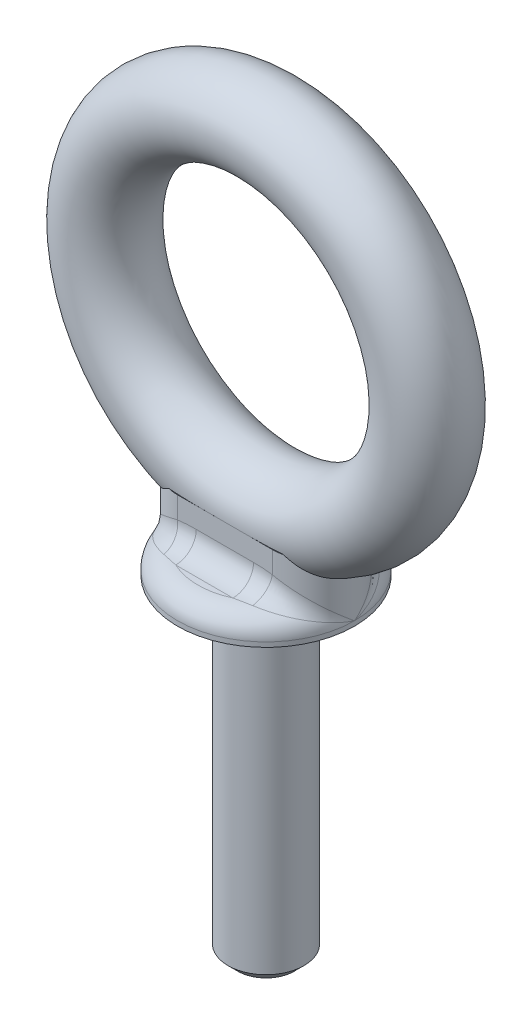
SolidWorks part; units mm, degrees
ref_plane "Front Plane" through (0, 0, 0) normal (0, 0, 1) x (1, 0, 0)
ref_plane "Top Plane" through (0, 0, 0) normal (0, 1, 0) x (1, 0, 0)
ref_plane "Right Plane" through (0, 0, 0) normal (1, 0, 0) x (0, 0, -1)
sketch "Sketch1" plane through (0, 0, 0) normal (0, 0, 1) x (1, 0, 0)
  line L0 (0, -26) -> (0, 0) construction
  line L1 (0, 0) -> (0, 2) construction
  line L2 (0, 2) -> (0, 8.5) construction
  line L3 (0, 8.5) -> (0, 27.5) construction
  line L4 (0, 27.5) -> (0, 34) construction
  line L5 (-3, -26) -> (3, -26) construction
  line L6 (-7, 0) -> (7, 0) construction
  line L7 (-3, 0) -> (3, 0) construction
  circle A0 centre (0, 18) radius 16 construction
  circle A1 centre (0, 18) radius 9.5 construction
  circle A2 centre (0, 30.75) radius 3.25 construction
  circle A3 centre (0, 5.25) radius 3.25 construction
  point P9 (0, 0)
  dimension "Eye Dia." = 19
  dimension "OD" = 32
  dimension "Dia." = 6.5
  dimension "Thread Size" = 6
  dimension "Thread Lg." = 26
  dimension "Shank Lg." = 26
  dimension "Overall Lg." = 60
  dimension "Shoulder Dia." = 14
sketch "Sketch2" plane through (0, 0, 0) normal (1, 0, 0) x (0, 0, -1)
  line L0 (-3.25, 18) -> (3.25, 18) construction
  line L1 (0, 34) -> (0, 27.5) construction
  line L2 (-3.25, 30.75) -> (3.25, 30.75) construction
  circle A0 centre (0, 30.75) radius 3.25
revolve "Revolve1" add sketch "Sketch2" angle 360 about L0
sketch "Sketch3" plane through (0, 0, 0) normal (0, 0, 1) x (1, 0, 0)
  line L0 (-7, 0) -> (0, 0)
  line L1 (0, 0) -> (0, 2)
  line L4 (-7, 0) -> (-7, 2)
  line L5 (0, 2) -> (-7, 2)
revolve "Revolve2" add sketch "Sketch3" angle 360 about L1
fillet "Fillet1" radius 1.625 1 edges at (7, 2, 0)
sketch "Sketch4" plane through (0, 0, 0) normal (0, 1, 0) x (1, 0, 0)
  line L0 (-3.75, 0) -> (3.75, 0) construction
  line L1 (-3.75, 3.25) -> (3.75, 3.25)
  line L2 (-3.75, -3.25) -> (3.75, -3.25)
  arc A0 (-3.75, 3.25) -> (-3.75, -3.25) centre (-3.75, 0) ccw
  arc A1 (3.75, -3.25) -> (3.75, 3.25) centre (3.75, 0) ccw
  circle A2 centre (0, 0) radius 7 construction
  point P2 (0, 0)
extrude "Boss-Extrude3" add sketch "Sketch4" along normal up to vertex (5.25 mm away) up to point (0, 5.25, 0)
fillet "Fillet2" radius 1.625 8 edges at (5.9807, 1.6103, 2.3636) (4.0355, 2, 3.2374) (-4.0355, 2, 3.2374) (0, 2, 3.25) (-5.9807, 1.6103, -2.3636) (-4.0355, 2, -3.2374) (4.0355, 2, -3.2374) (0, 2, -3.25)
sketch "Sketch5" plane through (0, 0, 0) normal (0, -1, 0) x (1, 0, 0)
  circle A0 centre (0, 0) radius 3
extrude "Boss-Extrude2" add sketch "Sketch5" along normal up to vertex (26 mm away) up to point (0, -26, 0)
ref_plane "Plane1" through (0, 0, 0) normal (0, -1, 0) x (1, 0, 0)
split "Split1" trim tools "Plane1" resulting bodies 105 106
sketch "Sketch6" plane through (0, -26, 0) normal (0, -1, 0) x (1, 0, 0)
  circle A1 centre (0, 0) radius 3
  circle A2 centre (0, 0) radius 3
  point P0 (3, 0)
  point P1 (0, -3)
  dimension "D1" = 0
sketch "Sketch7" plane through (0, 0, 0) normal (0, 0, 1) x (1, 0, 0)
  line L0 (3.1083, -25.9375) -> (3.1083, -26.9375) construction
  line L1 (3.1083, -26.9375) -> (2.2422, -26.4375) construction
  line L2 (2.2422, -26.4375) -> (3.1083, -25.9375) construction
  line L3 (2.3505, -26.375) -> (2.3505, -26.5) construction
  line L4 (3, -26) -> (3, -26.875) construction
  line L5 (2.2422, -26.4375) -> (2.3505, -26.4375) construction
  line L6 (3, -26.4375) -> (3.1083, -26.4375) construction
  line L7 (3.0541, -25.9688) -> (2.3505, -26.375)
  line L8 (2.3505, -26.375) -> (2.3505, -26.5)
  line L9 (2.3505, -26.5) -> (3.0541, -26.9062)
  line L10 (3.0541, -26.9062) -> (3.0541, -25.9688)
  point P13 (3.0541, -26.4375)
  dimension "D1" = 1
  dimension "D2" = 0.125
sketch "Sketch8" plane through (0, -26, 0) normal (0, -1, 0) x (1, 0, 0)
  circle A0 centre (0, 0) radius 2.2422
extrude "Cut-Extrude1" cut sketch "Sketch8" against normal up to vertex (26 mm away) draft 45 flip side to cut up to point (0, 0, 0)
combine bodies "Combine1" operation type add bodies to combine 108 106
sketch "SketchY" plane through (0, 0, 0) normal (1, 0, 0) x (0, 0, -1)
  line L0 (3, -26) -> (3, -6.5) construction
  dimension "D1" = 19.5
ref_plane "Plane2" through (0, -10, 0) normal (0, -1, 0) x (-1, 0, 0)
equation "\"D1@Fillet2\" = \"D1@Fillet1\""
equation "\"D2@Sketch7\" = \"D1@Sketch7\" / 8"
